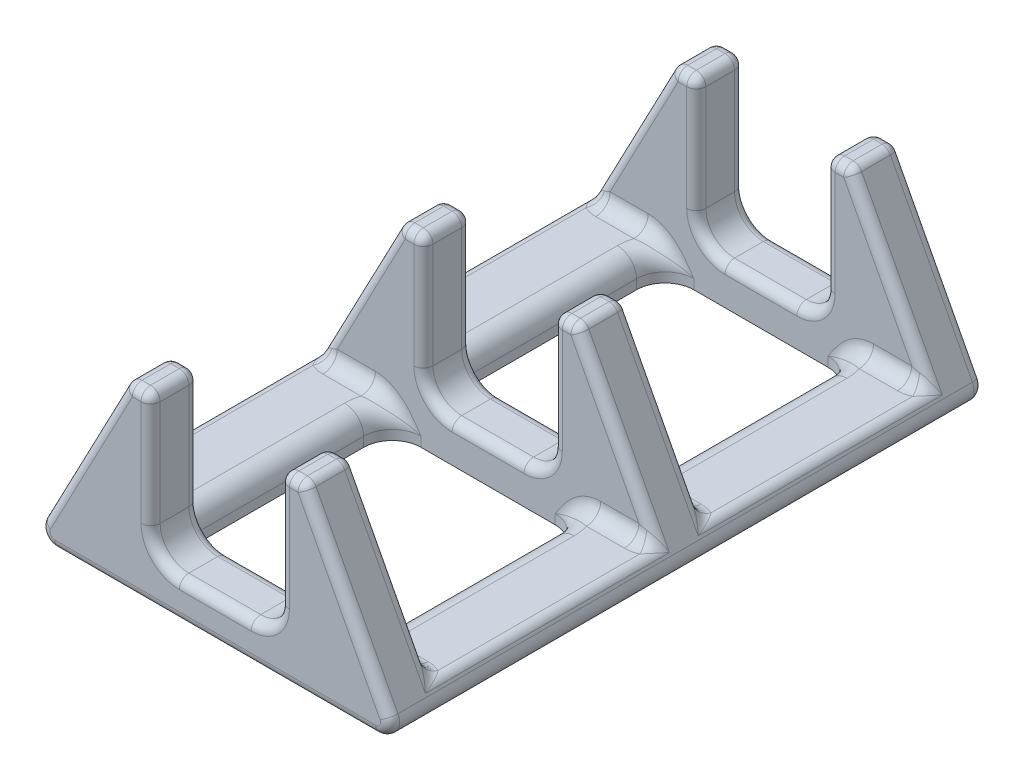
SolidWorks part; units mm, degrees
ref_plane "Front Plane" through (0, 0, 0) normal (0, 0, 1) x (1, 0, 0)
ref_plane "Top Plane" through (0, 0, 0) normal (0, 1, 0) x (1, 0, 0)
ref_plane "Right Plane" through (0, 0, 0) normal (1, 0, 0) x (0, 0, -1)
sketch "Sketch1" plane through (0, 0, 0) normal (0, 0, 1) x (1, 0, 0)
  line L0 (15.5, 15) -> (17.2925, 15)
  line L2 (-13.5, 13) -> (-13.5, -9)
  line L3 (-7.5, -15) -> (7.5, -15)
  line L4 (13.5, 13) -> (13.5, -9)
  line L5 (-13.5, 15) -> (13.5, -15) construction
  line L6 (-13.5, -15) -> (13.5, 15) construction
  line L7 (19.0624, 13.9315) -> (36.1857, -18.6028)
  line L8 (33.5309, -23) -> (-33.5309, -23)
  line L9 (-36.1857, -18.6028) -> (-19.0624, 13.9315)
  line L10 (-17.2925, 15) -> (-15.5, 15)
  arc A0 (-13.5, -9) -> (-7.5, -15) centre (-7.5, -9) ccw
  arc A1 (7.5, -15) -> (13.5, -9) centre (7.5, -9) ccw
  arc A2 (36.1857, -18.6028) -> (33.5309, -23) centre (33.5309, -20) cw
  arc A3 (-33.5309, -23) -> (-36.1857, -18.6028) centre (-33.5309, -20) cw
  arc A4 (17.2925, 15) -> (19.0624, 13.9315) centre (17.2925, 13) cw
  arc A5 (15.5, 15) -> (13.5, 13) centre (15.5, 13) ccw
  arc A6 (-15.5, 15) -> (-13.5, 13) centre (-15.5, 13) cw
  arc A7 (-19.0624, 13.9315) -> (-17.2925, 15) centre (-17.2925, 13) cw
  point P0 (0, 0)
  point P18 (38.5, -23)
  point P21 (-38.5, -23)
  point P24 (18.5, 15)
  point P33 (-18.5, 15)
  dimension "D8" = 6
  dimension "D9" = 3
  dimension "D10" = 2
  dimension "D1" = 27
  dimension "D2" = 30
  dimension "D3" = 5
  dimension "D4" = 5
  dimension "D5" = 25
  dimension "D6" = 25
  dimension "D7" = 8
  dimension "D11" = 30
extrude "Boss-Extrude1" add sketch "Sketch1" along normal blind 124
sketch "Sketch2" plane through (0, 0, 0) normal (1, 0, 0) x (0, 0, -1)
  line L0 (-124, -2.3356) -> (0, -2.3356) construction
  line L1 (-124, -18.6028) -> (-124, 13.9315) construction
  line L2 (0, -18.6028) -> (0, 13.9315) construction
  line L3 (-114, 15) -> (-114, -17)
  line L4 (-124, 15) -> (0, 15) construction
  line L5 (-114, -17) -> (-67, -17)
  line L6 (-67, -17) -> (-67, 15)
  line L7 (-67, 15) -> (-57, 15)
  line L8 (-57, 15) -> (-57, -17)
  line L9 (-57, -17) -> (-10, -17)
  line L10 (-10, -17) -> (-10, 15)
  line L11 (-10, 15) -> (-10, 33.4712)
  line L12 (-10, 33.4712) -> (-114, 33.4712)
  line L13 (-114, 33.4712) -> (-114, 15)
  line L14 (-124, -23) -> (0, -23) construction
  point P10 (-62, -2.3356)
  dimension "D1" = 5
  dimension "D2" = 5
  dimension "D3" = 10
  dimension "D4" = 10
  dimension "D5" = 6
  dimension "D6" = 6
extrude "Cut-Extrude1" cut sketch "Sketch2" against normal through all and the other way through all contours L13 L3 L5 L6 L7 L8 L9 L10 L11 L12
fillet "Fillet1" radius 2 88 edges at (36.0991, -21.5505, 0) (0, -23, 0) (-36.0991, -21.5505, 0) (-27.624, -2.3356, 0) (-18.3262, 14.7122, 0) (-16.3963, 15, 0) (-14.0858, 14.4142, 0) (-13.5, 2, 0) (-11.7426, -13.2426, 0) (0, -15, 0) (11.7426, -13.2426, 0) (13.5, 2, 0) (14.0858, 14.4142, 0) (16.3963, 15, 0) (18.3262, 14.7122, 0) (-27.2022, -1.5343, 10) (-18.3262, 14.7122, 10) (-16.3963, 15, 10) (-14.0858, 14.4142, 10) (-13.5, 2, 10) (-11.7426, -13.2426, 10) (0, -15, 10) (11.7426, -13.2426, 10) (13.5, 2, 10) (14.0858, 14.4142, 10) (16.3963, 15, 10) (18.3262, 14.7122, 10) (-27.2022, -1.5343, 57) (-18.3262, 14.7122, 57) (-16.3963, 15, 57) (-14.0858, 14.4142, 57) (-13.5, 2, 57) (-11.7426, -13.2426, 57) (0, -15, 57) (11.7426, -13.2426, 57) (13.5, 2, 57) (14.0858, 14.4142, 57) (16.3963, 15, 57) (18.3262, 14.7122, 57) (-27.2022, -1.5343, 67) (-18.3262, 14.7122, 67) (-16.3963, 15, 67) (-14.0858, 14.4142, 67) (-13.5, 2, 67) (-11.7426, -13.2426, 67) (0, -15, 67) (11.7426, -13.2426, 67) (13.5, 2, 67) (14.0858, 14.4142, 67) (16.3963, 15, 67) (18.3262, 14.7122, 67) (-11.7426, -13.2426, 124) (0, -15, 124) (11.7426, -13.2426, 124) (13.5, 2, 124) (14.0858, 14.4142, 124) (16.3963, 15, 124) (18.3262, 14.7122, 124) (27.624, -2.3356, 124) (36.0991, -21.5505, 124) (0, -23, 124) (-36.0991, -21.5505, 124) (-27.624, -2.3356, 124) (-18.3262, 14.7122, 124) (-16.3963, 15, 124) (-14.0858, 14.4142, 124) (27.2022, -1.5343, 114) (18.3262, 14.7122, 114) (16.3963, 15, 114) (14.0858, 14.4142, 114) (13.5, 2, 114) (11.7426, -13.2426, 114) (0, -15, 114) (-11.7426, -13.2426, 114) (-27.2022, -1.5343, 114) (-18.3262, 14.7122, 114) (-16.3963, 15, 114) (-14.0858, 14.4142, 114) (-35.3421, -17, 90.5) (-35.3421, -17, 33.5) (27.624, -2.3356, 0) (27.2022, -1.5343, 10) (35.3421, -17, 33.5) (27.2022, -1.5343, 57) (27.2022, -1.5343, 67) (35.3421, -17, 90.5) (-13.5, 2, 124) (-13.5, 2, 114)
sketch "Sketch3" plane through (0, 0, 0) normal (0, 1, 0) x (1, 0, 0)
  line L0 (0, -10) -> (0, -57) construction
  line L1 (-7.5, -10) -> (7.5, -10) construction
  line L2 (-7.5, -57) -> (7.5, -57) construction
  line L3 (0, -57) -> (0, -67) construction
  line L4 (-7.5, -67) -> (7.5, -67) construction
  line L5 (0, -67) -> (0, -114) construction
  line L6 (-7.5, -114) -> (7.5, -114) construction
  line L7 (7.5, -114) -> (33.082, -114) construction
  line L8 (-20, -67) -> (20, -67)
  line L9 (-20, -67) -> (-20, -114)
  line L10 (-20, -114) -> (20, -114)
  line L11 (20, -67) -> (20, -114)
  line L12 (-20, -67) -> (20, -114) construction
  line L13 (-20, -114) -> (20, -67) construction
  line L14 (7.5, -57) -> (33.082, -57) construction
  line L15 (-20, -10) -> (20, -10)
  line L16 (-20, -10) -> (-20, -57)
  line L17 (-20, -57) -> (20, -57)
  line L18 (20, -10) -> (20, -57)
  line L19 (-20, -10) -> (20, -57) construction
  line L20 (-20, -57) -> (20, -10) construction
  point P6 (0, -90.5)
  point P19 (0, -33.5)
  dimension "D1" = 40
  dimension "D2" = 40
extrude "Cut-Extrude2" cut sketch "Sketch3" against normal through all
fillet "Fillet2" radius 6 8 edges at (20, -20, 114) (-20, -20, 114) (-20, -20, 67) (20, -20, 67) (20, -20, 10) (-20, -20, 10) (20, -20, 57) (-20, -20, 57)
fillet "Fillet3" radius 4 12 edges at (18.2426, -17, 68.7574) (20, -17, 90.5) (-18.2426, -17, 68.7574) (-20, -17, 90.5) (-18.2426, -17, 11.7574) (-20, -17, 33.5) (18.2426, -17, 11.7574) (20, -17, 33.5) (18.2426, -17, 112.2426) (-18.2426, -17, 112.2426) (-18.2426, -17, 55.2426) (18.2426, -17, 55.2426)
fillet "Fillet4" radius 3 32 edges at (20, -17.2979, 114) (35.1683, -17.2878, 114.9663) (33.6242, -17, 114.0584) (-35.1683, -17.2878, 114.9663) (-33.6242, -17, 114.0584) (-20, -17.2979, 114) (20, -17.2979, 67) (35.1683, -17.2878, 66.0337) (33.6242, -17, 66.9416) (-35.1683, -17.2878, 66.0337) (-33.6242, -17, 66.9416) (-20, -17.2979, 67) (20, -17.2979, 57) (35.1683, -17.2878, 57.9663) (33.6242, -17, 57.0584) (-35.1683, -17.2878, 57.9663) (-33.6242, -17, 57.0584) (-20, -17.2979, 57) (20, -17.2979, 10) (35.1683, -17.2878, 9.0337) (33.6242, -17, 9.9416) (-35.1683, -17.2878, 9.0337) (-33.6242, -17, 9.9416) (-20, -17.2979, 10) (27.541, -17, 114) (-27.541, -17, 114) (27.541, -17, 67) (-27.541, -17, 67) (27.541, -17, 57) (-27.541, -17, 57) (27.541, -17, 10) (-27.541, -17, 10)
